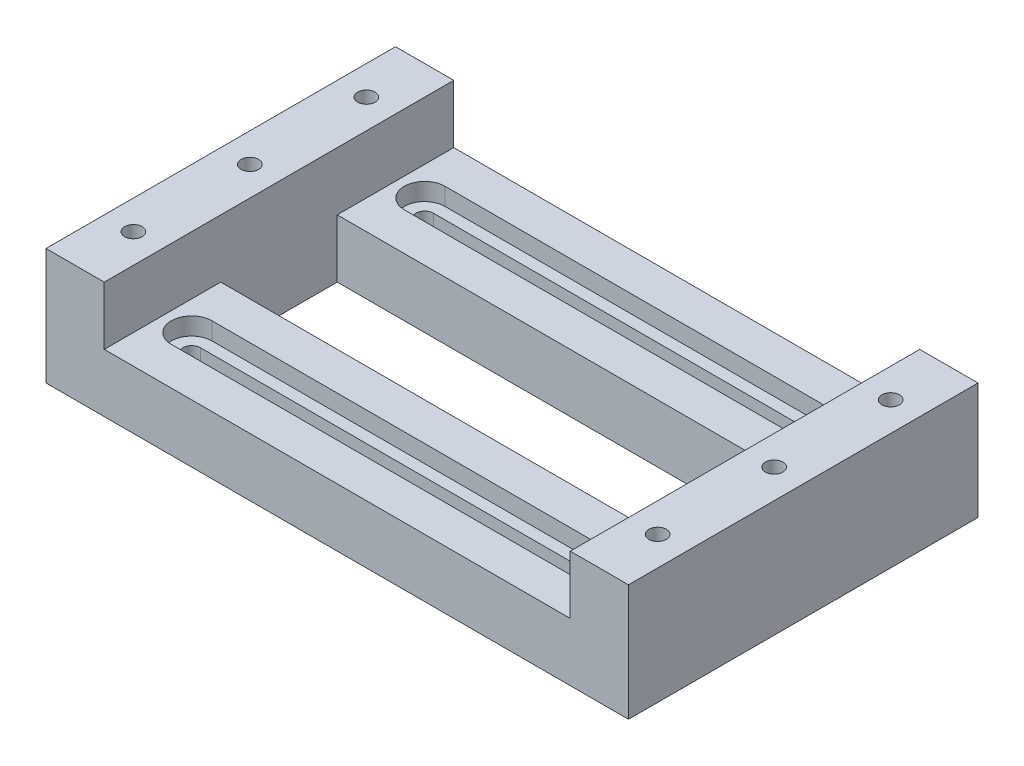
SolidWorks part; units mm, degrees
ref_plane "Front Plane" through (0, 0, 0) normal (0, 0, 1) x (1, 0, 0)
ref_plane "Top Plane" through (0, 0, 0) normal (0, 1, 0) x (1, 0, 0)
ref_plane "Right Plane" through (0, 0, 0) normal (1, 0, 0) x (0, 0, -1)
sketch "Sketch1" plane through (0, 0, 0) normal (0, 1, 0) x (1, 0, 0)
  line L0 (10, 40) -> (10, 20)
  line L1 (0, 0) -> (100, 0)
  line L2 (0, 0) -> (0, 60)
  line L3 (0, 60) -> (100, 60)
  line L4 (100, 0) -> (100, 60)
  line L5 (10, 20) -> (90, 20)
  line L6 (90, 20) -> (90, 40)
  line L7 (90, 40) -> (10, 40)
  line L8 (85, 51.5) -> (15, 51.5)
  line L9 (85, 48.5) -> (15, 48.5)
  line L10 (85, 8.5) -> (15, 8.5)
  line L11 (85, 11.5) -> (15, 11.5)
  circle A2 centre (5, 30) radius 1.5
  circle A7 centre (5, 50) radius 1.5
  circle A29 centre (5, 10) radius 1.5
  circle A30 centre (15, 50) radius 1.5
  circle A31 centre (15, 10) radius 1.5
  circle A44 centre (85, 50) radius 1.5
  circle A45 centre (85, 10) radius 1.5
  circle A46 centre (95, 50) radius 1.5
  circle A47 centre (95, 10) radius 1.5
  circle A48 centre (95, 30) radius 1.5
  dimension "D7" = 3
  dimension "D25" = 3
  dimension "D4" = 3
  dimension "D10" = 3
  dimension "D18" = 3
  dimension "D19" = 3
  dimension "D20" = 3
  dimension "D21" = 3
  dimension "D1" = 60
  dimension "D2" = 100
  dimension "D3" = 10
  dimension "D14" = 5
  dimension "D15" = 30
  dimension "D22" = 20
  dimension "D23" = 20
  dimension "D24" = 10
  dimension "D28" = 10
  dimension "D5" = 10
  dimension "D6" = 5
  dimension "D8" = 5
  dimension "D11" = 5
  dimension "D12" = 30
  dimension "D9" = 10
  dimension "D13" = 5
  dimension "D16" = 5
  dimension "D17" = 10
  dimension "D26" = 10
  dimension "D27" = 10
extrude "Boss-Extrude1" add sketch "Sketch1" along normal blind 10 contours L1 L4 L3 L2 A48 A47 A46 A45 A44 L9 A30 L8 A31 A29 A7 A2 L7 L6 L5 L0 region at (1.1662, 0, -30)
sketch "Sketch3" plane through (0, 10, 0) normal (0, 1, 0) x (1, 0, 0)
  line L9 (15, 46.5) -> (85, 46.5)
  line L10 (85, 53.5) -> (15, 53.5)
  line L11 (15, 46.5) -> (85, 46.5)
  line L12 (85, 53.5) -> (15, 53.5)
  line L22 (15, 6.5) -> (85, 6.5)
  line L23 (85, 13.5) -> (15, 13.5)
  line L24 (15, 6.5) -> (85, 6.5)
  line L25 (85, 13.5) -> (15, 13.5)
  arc A5 (85, 46.5) -> (85, 53.5) centre (85, 50) ccw
  arc A6 (15, 53.5) -> (15, 46.5) centre (15, 50) ccw
  arc A7 (85, 46.5) -> (85, 53.5) centre (85, 50) ccw
  arc A8 (15, 53.5) -> (15, 46.5) centre (15, 50) ccw
  arc A14 (85, 6.5) -> (85, 13.5) centre (85, 10) ccw
  arc A15 (15, 13.5) -> (15, 6.5) centre (15, 10) ccw
  arc A16 (85, 6.5) -> (85, 13.5) centre (85, 10) ccw
  arc A17 (15, 13.5) -> (15, 6.5) centre (15, 10) ccw
  dimension "D1" = 2
  dimension "D2" = 2
extrude "Cut-Slot insets" cut sketch "Sketch3" against normal blind 3
sketch "Sketch5" plane through (0, 10, 0) normal (0, 1, 0) x (1, 0, 0)
  line L0 (10, 20) -> (10, 40)
  line L1 (10, 40) -> (10, 60)
  line L2 (0, 60) -> (100, 60) construction
  line L3 (10, 60) -> (0, 60)
  line L4 (0, 60) -> (0, 0)
  line L5 (0, 0) -> (10, 0)
  line L6 (0, 0) -> (100, 0) construction
  line L7 (10, 0) -> (10, 20)
  line L8 (90, 20) -> (90, 0)
  line L9 (90, 0) -> (100, 0)
  line L10 (100, 0) -> (100, 60)
  line L11 (100, 60) -> (90, 60)
  line L18 (90, 60) -> (90, 40)
  line L19 (90, 40) -> (90, 20)
  circle A0 centre (95, 50) radius 1.5
  circle A1 centre (95, 30) radius 1.5
  circle A3 centre (95, 10) radius 1.5
  circle A5 centre (5, 10) radius 1.5
  circle A7 centre (5, 30) radius 1.5
  circle A8 centre (5, 50) radius 1.5
extrude "Boss-Extrude3" add sketch "Sketch5" along normal blind 10
sketch "Sketch6" plane through (0, 0, 0) normal (0, -1, 0) x (1, 0, 0)
  circle A0 centre (5, -50) radius 3.75
  circle A1 centre (5, -30) radius 3.75
  circle A2 centre (5, -10) radius 3.75
  circle A3 centre (95, -10) radius 3.75
  circle A4 centre (95, -30) radius 3.75
  circle A5 centre (95, -50) radius 3.75
  dimension "D1" = 7.5
  dimension "D2" = 7.5
  dimension "D3" = 7.5
  dimension "D4" = 7.5
  dimension "D5" = 7.5
  dimension "D6" = 7.5
extrude "Cut-Extrude1" cut sketch "Sketch6" against normal blind 2.5
equation "\"boltdiameter\"=3"
equation "\"D25@Sketch1\"=\"boltdiameter\""
equation "\"D4@Sketch1\"=\"boltdiameter\""
equation "\"D10@Sketch1\"=\"boltdiameter\""
equation "\"D7@Sketch1\"=\"boltdiameter\""
equation "\"D18@Sketch1\"=\"boltdiameter\""
equation "\"D19@Sketch1\"=\"boltdiameter\""
equation "\"boltfacediameter\"=7"
equation "\"D20@Sketch1\"=\"boltdiameter\""
equation "\"D21@Sketch1\"=\"boltdiameter\""
equation "\"boltfacediam\"=2"
equation "\"D1@Sketch3\"=\"boltfacediam\""
equation "\"D2@Sketch3\"=\"boltfacediam\""
equation "\"screwInset\"=7.5"
equation "\"D1@Sketch6\"=\"screwInset\""
equation "\"D2@Sketch6\"=\"screwInset\""
equation "\"D3@Sketch6\"=\"screwInset\""
equation "\"D4@Sketch6\"=\"screwInset\""
equation "\"D5@Sketch6\"=\"screwInset\""
equation "\"D6@Sketch6\"=\"screwInset\""
